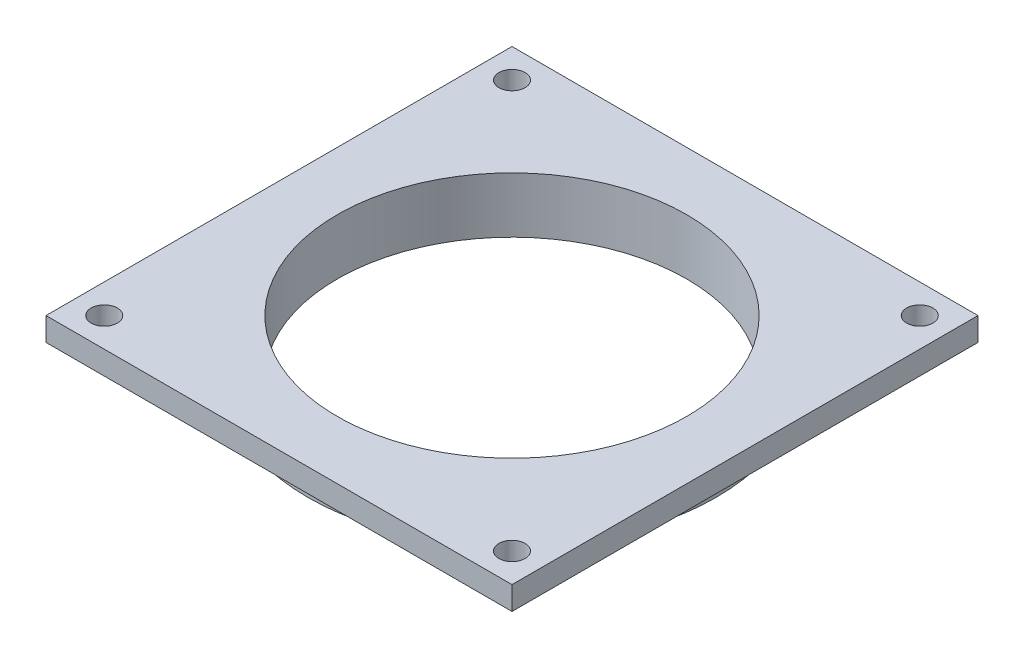
SolidWorks part; units mm, degrees
ref_plane "Front Plane" through (0, 0, 0) normal (0, 0, 1) x (1, 0, 0)
ref_plane "Top Plane" through (0, 0, 0) normal (0, 1, 0) x (1, 0, 0)
ref_plane "Right Plane" through (0, 0, 0) normal (1, 0, 0) x (0, 0, -1)
sketch "Sketch1" plane through (0, 0, 0) normal (0, 1, 0) x (1, 0, 0)
  circle A0 centre (0, 0) radius 35
  circle A1 centre (0, 0) radius 30
extrude "Boss-Extrude1" add sketch "Sketch1" along normal blind 5.5626
sketch "Sketch2" plane through (0, 5.5626, 0) normal (0, 1, 0) x (1, 0, 0)
  line L1 (35, -35) -> (-35, -35)
  line L2 (35, -35) -> (35, 35)
  line L3 (35, 35) -> (-35, 35)
  line L4 (-35, -35) -> (-35, 35)
  line L5 (35, -35) -> (-35, 35) construction
  line L6 (35, 35) -> (-35, -35) construction
  line L7 (40, -40) -> (-40, -40)
  line L8 (40, -40) -> (40, 40)
  line L9 (40, 40) -> (-40, 40)
  line L10 (-40, -40) -> (-40, 40)
  line L11 (40, -40) -> (-40, 40) construction
  line L12 (40, 40) -> (-40, -40) construction
  circle A0 centre (-35, 35) radius 2.25
  circle A1 centre (35, 35) radius 2.25
  circle A2 centre (35, -35) radius 2.25
  circle A3 centre (-35, -35) radius 2.25
  circle A4 centre (0, 0) radius 30
  point P0 (0, 0)
  point P6 (0, 0)
  circle M7 centre (0, 0) radius 35
  circle M8 centre (0, 0) radius 30
  dimension "D1" = 70
  dimension "D2" = 70
  dimension "D3" = 5
  dimension "D4" = 5
extrude "Boss-Extrude3" add sketch "Sketch2" along normal blind 4 contours M7 M8 | A0 L4 L3 M7 | A1 L3 L2 M7 | A2 L2 L1 M7 | A3 L1 L4 M7 | L10 L7 L8 L9 A3 L4 A0 L3 A1 L2 A2 L1 region at (-27.0767, 5.5626, 27.0767) region at (27.0767, 5.5626, 27.0767) region at (-24.0487, 5.5626, 24.0487) region at (-27.0767, 5.5626, -27.0767) region at (27.0767, 5.5626, -27.0767) region at (0, 5.5626, 38.8686)
